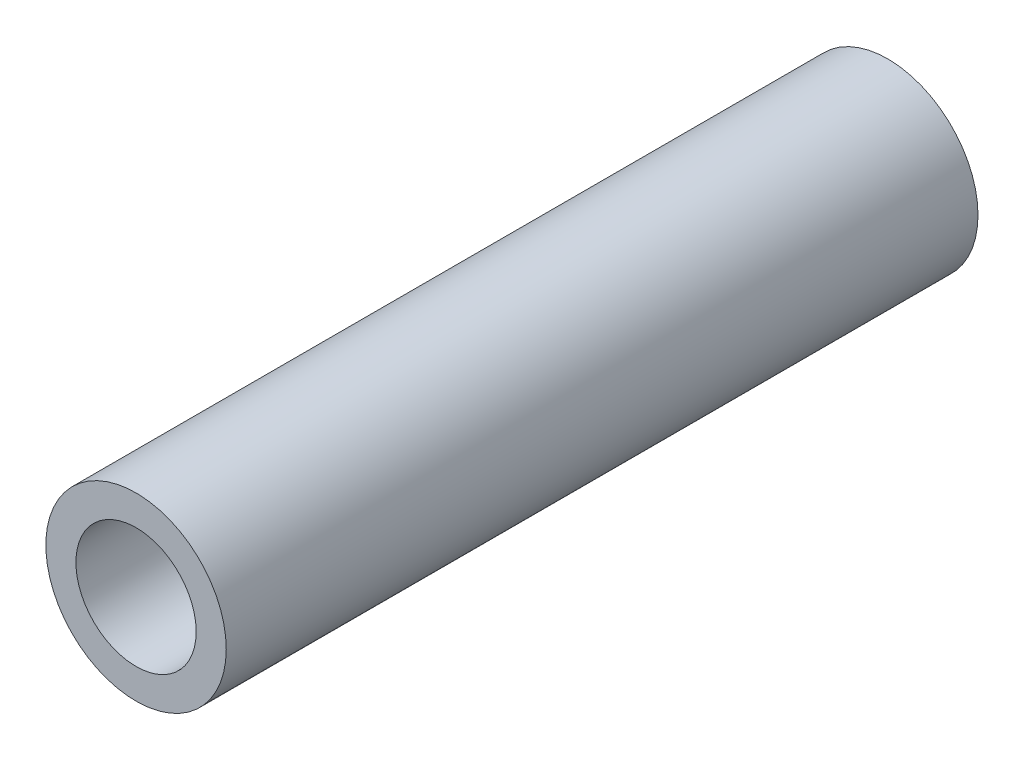
SolidWorks part; units mm, degrees
ref_plane "Front Plane" through (0, 0, 0) normal (0, 0, 1) x (1, 0, 0)
ref_plane "Top Plane" through (0, 0, 0) normal (0, 1, 0) x (1, 0, 0)
ref_plane "Right Plane" through (0, 0, 0) normal (1, 0, 0) x (0, 0, -1)
sketch "Real Length Sketch" plane through (0, 0, 0) normal (1, 0, 0) x (0, 0, -1)
  point P0 (0, 0)
  point P1 (200, 0)
  dimension "Length" = 200
sketch "Cross Section Sketch" plane through (0, 0, 0) normal (0, 0, 1) x (1, 0, 0)
  circle A0 centre (0, 0) radius 3
  circle A1 centre (0, 0) radius 2
  dimension "OD" = 6
  dimension "ID" = 4
extrude "Extrude Length" add sketch "Cross Section Sketch" along normal mid plane 25
